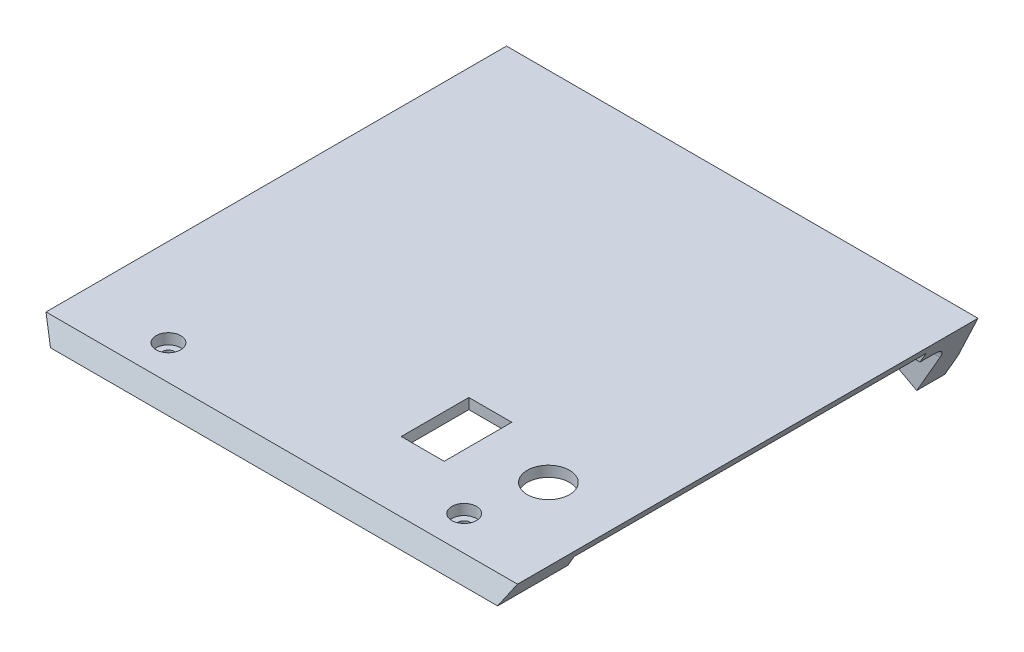
SolidWorks part; units mm, degrees
ref_plane "Front Plane" through (0, 0, 0) normal (0, 0, 1) x (1, 0, 0)
ref_plane "Top Plane" through (0, 0, 0) normal (0, 1, 0) x (1, 0, 0)
ref_plane "Right Plane" through (0, 0, 0) normal (1, 0, 0) x (0, 0, -1)
sketch "Sketch1" plane through (0, 0, 0) normal (0, 1, 0) x (1, 0, 0)
  line L0 (0, 64) -> (0, -64) construction
  line L1 (-63.5, 64) -> (63.5, 64)
  line L2 (-63.5, 64) -> (-63.5, -64)
  line L3 (-63.5, -64) -> (63.5, -64)
  line L4 (63.5, 64) -> (63.5, -64)
  line L5 (-63.5, 64) -> (63.5, -64) construction
  line L6 (-63.5, -64) -> (63.5, 64) construction
  circle A0 centre (-42, -52) radius 1.7
  circle A1 centre (42, -52) radius 1.7
  point P0 (0, 0)
  dimension "D7" = 3.4
  dimension "D8" = 3.4
  dimension "D1" = 127
  dimension "D2" = 12
  dimension "D3" = 12
  dimension "D4" = 42
  dimension "D5" = 42
  dimension "D6" = 128
extrude "Boss-Extrude2" add sketch "Sketch1" along normal blind 6
sketch "Sketch2" plane through (0, 0, -64) normal (0, 0, -1) x (-1, 0, 0)
  line L0 (0, 0) -> (0, -111) construction
  line L1 (-63.5, 6) -> (-63.5, -21.1793)
  line L2 (63.5, 6) -> (63.5, -21.1793)
  line L4 (63.5, 6) -> (-63.5, 6)
  arc A1 (63.5, -21.1793) -> (-63.5, -21.1793) centre (0, -111) ccw
  dimension "D2" = 220
extrude "Boss-Extrude3" add sketch "Sketch2" along normal blind 8
sketch "Sketch3" plane through (0, 6, 0) normal (0, 1, 0) x (1, 0, 0)
  circle A0 centre (42, -52) radius 3.5
  circle A1 centre (-42, -52) radius 3.5
  dimension "D1" = 7
  dimension "D2" = 7
extrude "Cut-Extrude1" cut sketch "Sketch3" against normal blind 3
fillet "Chamfer1" radius 3 1 edges at (0, 6, -72)
draft "Draft2" type of draft neutral plane draft angle 30 neutral plane "Top Plane" faces to draft 1 face at (-63.5, -5.6227, -30.4286) neutral plane through (0, 0, 0) neutral plane normal (0, 1, 0) reverse direction yes parameters "D1"=30
draft "Draft3" type of draft neutral plane draft angle 30 neutral plane "Top Plane" faces to draft 1 face at (63.5, -5.6227, -30.4286) neutral plane through (0, 0, 0) neutral plane normal (0, 1, 0) reverse direction yes parameters "D1"=30
fillet "Fillet5" radius 4 1 edges at (0, 0, -64)
draft "Draft4" type of draft neutral plane draft angle 20 neutral plane "Top Plane" faces to draft 1 face at (0, 3, 64) neutral plane through (0, 0, 0) neutral plane normal (0, 1, 0) parameters "D1"=20
sketch "Sketch4" plane through (0, 0, 0) normal (0, -1, 0) x (1, 0, 0)
  line L8 (-63.5, 64) -> (63.5, 64) construction
  line L9 (-83.5, 44) -> (83.5, 44)
  line L10 (-83.5, 44) -> (-83.5, -56)
  line L11 (-83.5, -56) -> (83.5, -56)
  line L12 (83.5, 44) -> (83.5, -56)
  line L13 (-63.5, -60) -> (-25.5147, -60) construction
  line L14 (-63.5, -60) -> (-63.5, 64) construction
  line L15 (63.5, 64) -> (63.5, -60) construction
  dimension "D1" = 20
  dimension "D2" = 4
  dimension "D3" = 20
  dimension "D4" = 20
extrude "Cut-Extrude2" cut sketch "Sketch4" against normal blind 3
sketch "Sketch5" plane through (0, 3, 0) normal (0, -1, 0) x (1, 0, 0)
  line L1 (63.5, 44) -> (-63.5, 44) construction
  line L3 (-65.2321, 32.4) -> (65.2321, 32.4) construction
  line L4 (14.1321, 42) -> (26.3321, 42)
  line L5 (14.1321, 42) -> (14.1321, 22.8)
  line L6 (14.1321, 22.8) -> (26.3321, 22.8)
  line L7 (26.3321, 42) -> (26.3321, 22.8)
  line L8 (14.1321, 42) -> (26.3321, 22.8) construction
  line L9 (14.1321, 22.8) -> (26.3321, 42) construction
  line L10 (-65.2321, 44) -> (-65.2321, -56) construction
  line L11 (65.2321, -56) -> (65.2321, 44) construction
  circle A0 centre (46.3321, 32.4) radius 6
  point P6 (20.2321, 32.4)
  point P19 (0, 0)
  point P20 (0, 0)
  dimension "D4" = 12
  dimension "D1" = 12.2
  dimension "D2" = 19.2
  dimension "D3" = 2
  dimension "D5" = 20
  dimension "D6" = 45
extrude "Cut-Extrude3" cut sketch "Sketch5" against normal blind 10
sketch "Sketch6" plane through (0, 3, 0) normal (0, -1, 0) x (1, 0, 0)
  line L0 (63.5, 44) -> (-63.5, 44) construction
  line L1 (-33.2321, 43) -> (-3.2321, 43)
  line L2 (-33.2321, 43) -> (-33.2321, 17)
  line L3 (-33.2321, 17) -> (-3.2321, 17)
  line L4 (-3.2321, 43) -> (-3.2321, 17)
  line L5 (-65.2321, 44) -> (-65.2321, -56) construction
  circle A0 centre (-12.2321, 39.5) radius 1.5
  circle A1 centre (-12.2321, 20.5) radius 1.5
  point P12 (-3.2321, 30)
  dimension "D5" = 3
  dimension "D6" = 3
  dimension "D1" = 30
  dimension "D2" = 26
  dimension "D3" = 1
  dimension "D4" = 32
  dimension "D7" = 9
  dimension "D8" = 9
  dimension "D9" = 9.5
  dimension "D10" = 9.5
extrude "Boss-Extrude4" add sketch "Sketch6" along normal blind 5
fillet "Fillet6" radius 2 4 edges at (-3.2321, 0.5, 43) (-33.2321, 0.5, 43) (-33.2321, 0.5, 17) (-3.2321, 0.5, 17)
